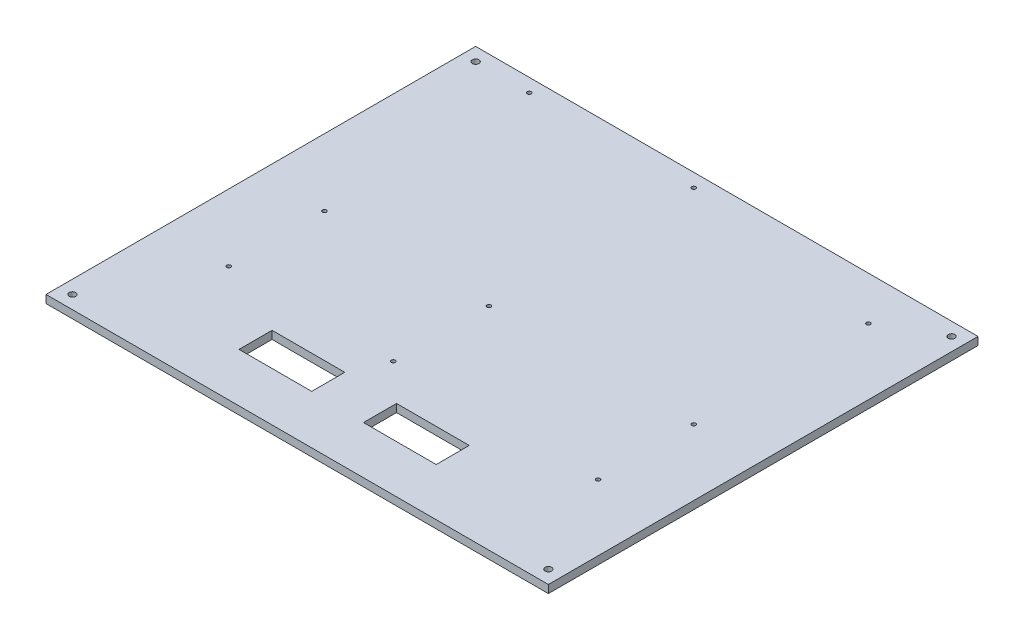
SolidWorks part; units mm, degrees
ref_plane "Front" through (0, 0, 0) normal (0, 0, 1) x (1, 0, 0)
ref_plane "Top" through (0, 0, 0) normal (0, 1, 0) x (1, 0, 0)
ref_plane "Right" through (0, 0, 0) normal (1, 0, 0) x (0, 0, -1)
sketch "Base Plate" plane through (0, 0, 0) normal (0, 1, 0) x (1, 0, 0)
  line L0 (-190, 162.5) -> (190, -162.5) construction
  line L1 (-190, 162.5) -> (190, 162.5)
  line L2 (-190, 162.5) -> (-190, -162.5)
  line L3 (-190, -162.5) -> (190, -162.5)
  line L4 (190, 162.5) -> (190, -162.5)
  line L5 (149, 162.5) -> (149, -162.5) construction
  line L6 (-155.8, 162.5) -> (-155.8, -162.5) construction
  line L7 (-155.8, -81.34) -> (149, -81.34) construction
  line L8 (-139.29, 162.5) -> (-139.29, -81.34) construction
  line L9 (14, -101.34) -> (69, -101.34)
  line L10 (14, -101.34) -> (14, -126.34)
  line L11 (14, -126.34) -> (69, -126.34)
  line L12 (69, -101.34) -> (69, -126.34)
  line L13 (-26, -100.5) -> (-81, -100.5)
  line L14 (-26, -100.5) -> (-26, -125.5)
  line L15 (-26, -125.5) -> (-81, -125.5)
  line L16 (-81, -100.5) -> (-81, -125.5)
  line L17 (-155.8, -74.99) -> (149, -74.99) construction
  line L18 (-155.8, 152.34) -> (149, 152.34) construction
  line L19 (-155.8, -2.6) -> (149, -2.6) construction
  line L20 (-14.83, 162.5) -> (-14.83, -81.34) construction
  line L21 (140.11, 162.5) -> (140.11, -81.34) construction
  circle A0 centre (-139.29, -74.99) radius 1.5
  circle A3 centre (-14.83, -2.6) radius 1.5
  circle A4 centre (-139.29, -2.6) radius 1.5
  circle A5 centre (-139.29, 152.34) radius 1.5
  circle A6 centre (-14.83, 152.34) radius 1.5
  circle A7 centre (-14.83, -74.99) radius 1.5
  circle A8 centre (140.11, -74.99) radius 1.5
  circle A9 centre (140.11, -2.6) radius 1.5
  circle A10 centre (140.11, 129.48) radius 1.5
  circle A11 centre (-180, -152.5) radius 2.5
  circle A12 centre (180, -152.5) radius 2.5
  circle A13 centre (-180, 152.5) radius 2.5
  circle A14 centre (180, 152.5) radius 2.5
  dimension "D14" = 3
  dimension "D15" = 10.16
  dimension "D22" = 5
  dimension "D1" = 325
  dimension "D2" = 380
  dimension "D3" = 41
  dimension "D4" = 304.8
  dimension "D5" = 154.94
  dimension "D6" = 243.84
  dimension "D7" = 80
  dimension "D8" = 55
  dimension "D9" = 25
  dimension "D10" = 20
  dimension "D11" = 40
  dimension "D12" = 55
  dimension "D13" = 16.51
  dimension "D16" = 279.4
  dimension "D17" = 227.33
  dimension "D18" = 124.46
  dimension "D19" = 22.86
  dimension "D20" = 10
  dimension "D21" = 10
  dimension "D23" = 10
  dimension "D24" = 10
  dimension "D25" = 10
  dimension "D26" = 10
  dimension "D27" = 10
  dimension "D28" = 10
extrude "Boss-Extrude1" add sketch "Base Plate" along normal blind 6
